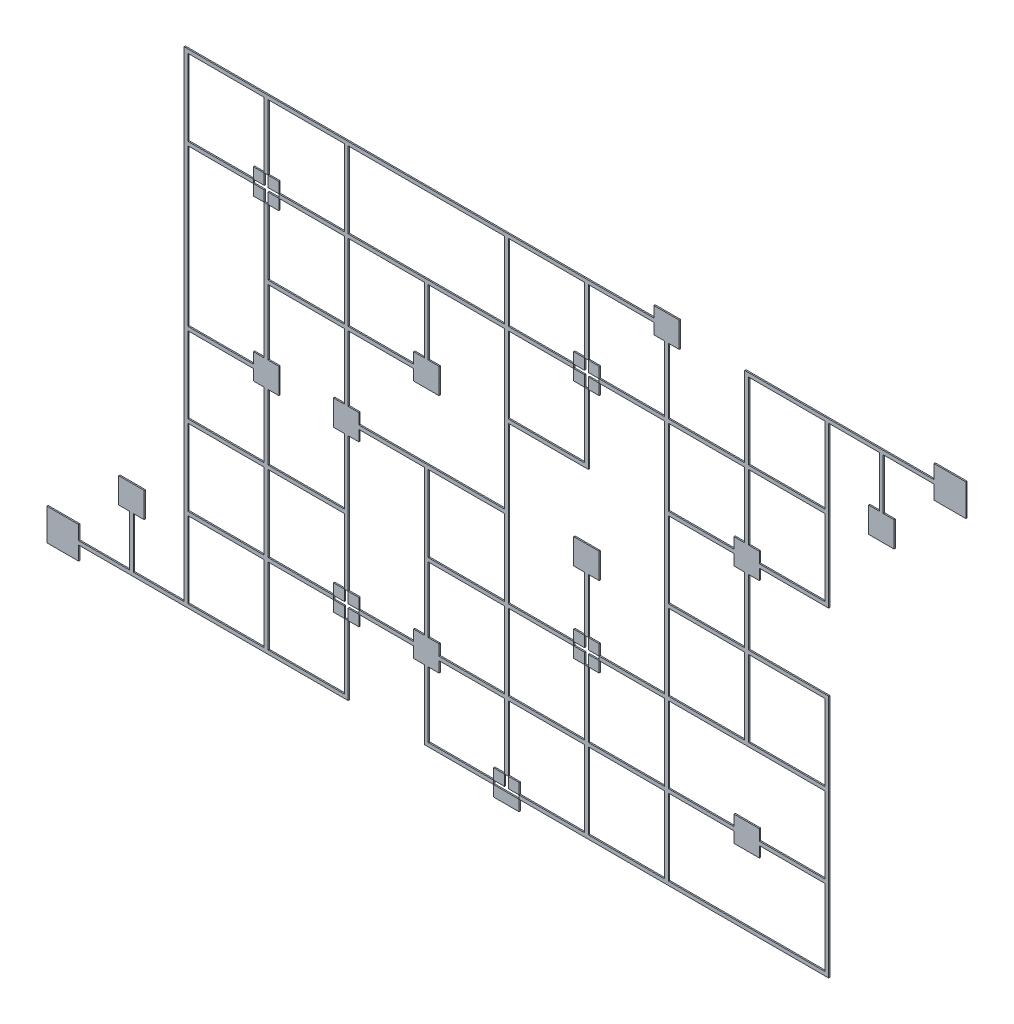
SolidWorks part; units mm, degrees
ref_plane "Front Plane" through (0, 0, 0) normal (0, 0, 1) x (1, 0, 0)
ref_plane "Top Plane" through (0, 0, 0) normal (0, 1, 0) x (1, 0, 0)
ref_plane "Right Plane" through (0, 0, 0) normal (1, 0, 0) x (0, 0, -1)
sketch "Sketch2" plane through (0, 0, 0) normal (0, 0, 1) x (1, 0, 0)
  line L1 (-2400, 2010) -> (2670, 2010)
  line L2 (-2400, 2010) -> (-2400, -1800)
  line L3 (-2400, -1800) -> (2670, -1800)
  line L4 (2670, 2010) -> (2670, -1800)
  dimension "D1" = 3810
  dimension "D2" = 5070
extrude "Boss-Extrude1" add sketch "Sketch2" along normal blind 10 contours L2 L3 L4 L1
sketch "Sketch3" plane through (0, 0, 10) normal (0, 0, 1) x (1, 0, 0)
  line L0 (-2400, 2010) -> (-2400, -1800) construction
  line L1 (-2370, 1980) -> (2640, 1980)
  line L2 (-2370, 1980) -> (-2370, -1770)
  line L3 (-2370, -1770) -> (2640, -1770)
  line L4 (2640, 1980) -> (2640, -1770)
  line L13 (-2400, -1800) -> (2670, -1800) construction
  line L14 (2670, 2010) -> (2670, -1800) construction
  line L15 (-2400, 2010) -> (2670, 2010) construction
  line L17 (-2370, 1980) -> (-1770, 1980)
  line L18 (-2370, 1980) -> (-2370, 1380)
  line L19 (-2370, 1380) -> (-1770, 1380)
  line L20 (-1770, 1980) -> (-1770, 1380)
  dimension "D1" = 30
  dimension "D2" = 30
  dimension "D3" = 30
  dimension "D4" = 30
  dimension "D5" = 600
  dimension "D6" = 600
sketch "Sketch4" plane through (0, 0, 0) normal (0, 0, 1) x (1, 0, 0)
extrude "Cut-Extrude14" cut sketch "Sketch3" against normal blind 20 contours L20 L1 L2 L19 region at (-2070, 1680, 10)
pattern_linear "LPattern2" count 8 spacing 630 along (1, 0, 0) count 6 spacing 630 along (0, -1, 0) of "Cut-Extrude14"
sketch "Sketch5" plane through (0, 0, 10) normal (0, 0, 1) x (1, 0, 0)
  line L0 (-2370, 1980) -> (-2370, 1380) construction
  line L1 (-1855, 1465) -> (-1655, 1465)
  line L2 (-1855, 1465) -> (-1855, 1265)
  line L3 (-1855, 1265) -> (-1655, 1265)
  line L4 (-1655, 1465) -> (-1655, 1265)
  line L6 (-2370, 1980) -> (-1770, 1980) construction
  dimension "D1" = 515
  dimension "D2" = 200
  dimension "D3" = 200
  dimension "D4" = 515
extrude "Boss-Extrude2" add sketch "Sketch5" against normal through all
sketch "Sketch6" plane through (0, 0, 0) normal (0, 0, 1) x (1, 0, 0)
  line L0 (-2370, -510) -> (-1770, -510) construction
  line L1 (-1855, 205) -> (-1655, 205)
  line L2 (-1855, 205) -> (-1855, 5)
  line L3 (-1855, 5) -> (-1655, 5)
  line L4 (-1655, 205) -> (-1655, 5)
  line L5 (-2370, 720) -> (-2370, 120) construction
  dimension "D1" = 515
  dimension "D2" = 200
  dimension "D3" = 200
  dimension "D4" = 515
extrude "Boss-Extrude3" add sketch "Sketch6" along normal blind 10
sketch "Sketch7" plane through (0, 0, 0) normal (0, 0, 1) x (1, 0, 0)
  line L0 (-1740, -510) -> (-1140, -510) construction
  line L1 (-1225, 205) -> (-1025, 205)
  line L2 (-1225, 205) -> (-1225, 5)
  line L3 (-1225, 5) -> (-1025, 5)
  line L4 (-1025, 205) -> (-1025, 5)
  line L5 (-510, 720) -> (-510, 120) construction
  dimension "D1" = 515
  dimension "D2" = 200
  dimension "D3" = 200
  dimension "D4" = 515
extrude "Boss-Extrude4" add sketch "Sketch7" along normal blind 10
sketch "Sketch8" plane through (0, 0, 0) normal (0, 0, 1) x (1, 0, 0)
  line L0 (-1740, -1770) -> (-1140, -1770) construction
  line L1 (-1225, -1055) -> (-1025, -1055)
  line L2 (-1225, -1055) -> (-1225, -1255)
  line L3 (-1225, -1255) -> (-1025, -1255)
  line L4 (-1025, -1055) -> (-1025, -1255)
  line L5 (-1740, -540) -> (-1740, -1140) construction
  dimension "D1" = 515
  dimension "D2" = 200
  dimension "D3" = 200
  dimension "D4" = 515
extrude "Boss-Extrude5" add sketch "Sketch8" along normal blind 10
sketch "Sketch9" plane through (0, 0, 0) normal (0, 0, 1) x (1, 0, 0)
  line L0 (-1110, -1770) -> (-510, -1770) construction
  line L1 (-595, -1055) -> (-395, -1055)
  line L2 (-595, -1055) -> (-595, -1255)
  line L3 (-595, -1255) -> (-395, -1255)
  line L4 (-395, -1055) -> (-395, -1255)
  line L5 (120, -540) -> (120, -1140) construction
  dimension "D1" = 515
  dimension "D2" = 200
  dimension "D3" = 200
  dimension "D4" = 515
extrude "Boss-Extrude6" add sketch "Sketch9" along normal blind 10
sketch "Sketch10" plane through (0, 0, 0) normal (0, 0, 1) x (1, 0, 0)
  line L0 (-1025, 120) -> (-510, 120) construction
  line L1 (-595, 835) -> (-395, 835)
  line L2 (-595, 835) -> (-595, 635)
  line L3 (-595, 635) -> (-395, 635)
  line L4 (-395, 835) -> (-395, 635)
  line L5 (-1110, 1350) -> (-1110, 750) construction
  dimension "D1" = 515
  dimension "D2" = 200
  dimension "D3" = 200
  dimension "D4" = 515
extrude "Boss-Extrude7" add sketch "Sketch10" along normal blind 10
sketch "Sketch11" plane through (0, 0, 0) normal (0, 0, 1) x (1, 0, 0)
  line L0 (150, 1980) -> (150, 1380) construction
  line L1 (665, 1465) -> (865, 1465)
  line L2 (665, 1465) -> (665, 1265)
  line L3 (665, 1265) -> (865, 1265)
  line L4 (865, 1465) -> (865, 1265)
  line L5 (150, 750) -> (750, 750) construction
  point P4 (665, 1365)
  dimension "D1" = 515
  dimension "D2" = 200
  dimension "D3" = 200
  dimension "D4" = 515
extrude "Boss-Extrude8" add sketch "Sketch11" along normal blind 10
sketch "Sketch12" plane through (0, 0, 0) normal (0, 0, 1) x (1, 0, 0)
  line L0 (865, 1380) -> (1380, 1380) construction
  line L1 (1295, 2095) -> (1495, 2095)
  line L2 (1295, 2095) -> (1295, 1895)
  line L3 (1295, 1895) -> (1495, 1895)
  line L4 (1495, 2095) -> (1495, 1895)
  line L5 (780, 1980) -> (780, 1465) construction
  dimension "D1" = 515
  dimension "D2" = 200
  dimension "D3" = 200
  dimension "D4" = 515
extrude "Boss-Extrude9" add sketch "Sketch12" along normal blind 10
sketch "Sketch13" plane through (0, 0, 0) normal (0, 0, 1) x (1, 0, 0)
  line L0 (1410, 120) -> (2010, 120) construction
  line L1 (1925, 835) -> (2125, 835)
  line L2 (1925, 835) -> (1925, 635)
  line L3 (1925, 635) -> (2125, 635)
  line L4 (2125, 835) -> (2125, 635)
  line L5 (1410, 1350) -> (1410, 750) construction
  dimension "D1" = 515
  dimension "D2" = 200
  dimension "D3" = 200
  dimension "D4" = 515
extrude "Boss-Extrude10" add sketch "Sketch13" along normal blind 10
sketch "Sketch14" plane through (0, 0, 0) normal (0, 0, 1) x (1, 0, 0)
  line L0 (150, 720) -> (150, 120) construction
  line L1 (665, 205) -> (865, 205)
  line L2 (665, 205) -> (665, 5)
  line L3 (665, 5) -> (865, 5)
  line L4 (865, 205) -> (865, 5)
  line L5 (150, -510) -> (750, -510) construction
  dimension "D1" = 515
  dimension "D2" = 200
  dimension "D3" = 200
  dimension "D4" = 515
extrude "Boss-Extrude11" add sketch "Sketch14" along normal blind 10
sketch "Sketch15" plane through (0, 0, 0) normal (0, 0, 1) x (1, 0, 0)
  line L0 (150, 90) -> (150, -510) construction
  line L1 (665, -425) -> (865, -425)
  line L2 (665, -425) -> (665, -625)
  line L3 (665, -625) -> (865, -625)
  line L4 (865, -425) -> (865, -625)
  line L5 (150, -1140) -> (750, -1140) construction
  dimension "D1" = 515
  dimension "D2" = 200
  dimension "D3" = 200
  dimension "D4" = 515
extrude "Boss-Extrude12" add sketch "Sketch15" along normal blind 10
sketch "Sketch17" plane through (0, 0, 0) normal (0, 0, 1) x (1, 0, 0)
  line L0 (1410, -540) -> (1410, -1140) construction
  line L1 (1925, -1055) -> (2125, -1055)
  line L2 (1925, -1055) -> (1925, -1255)
  line L3 (1925, -1255) -> (2125, -1255)
  line L4 (2125, -1055) -> (2125, -1255)
  line L5 (1410, -1770) -> (2010, -1770) construction
  dimension "D1" = 515
  dimension "D2" = 200
  dimension "D3" = 200
  dimension "D4" = 515
extrude "Boss-Extrude14" add sketch "Sketch17" along normal blind 10
sketch "Sketch18" plane through (0, 0, 0) normal (0, 0, 1) x (1, 0, 0)
  line L0 (-480, -1255) -> (-480, -1770) construction
  line L1 (35, -1685) -> (235, -1685)
  line L2 (35, -1685) -> (35, -1885)
  line L3 (35, -1885) -> (235, -1885)
  line L4 (235, -1685) -> (235, -1885)
  line L5 (-395, -1170) -> (120, -1170) construction
  dimension "D1" = 515
  dimension "D2" = 200
  dimension "D3" = 200
  dimension "D4" = 515
extrude "Boss-Extrude15" add sketch "Sketch18" along normal blind 10
sketch "Sketch19" plane through (0, 0, 0) normal (0, 0, 1) x (1, 0, 0)
  line L1 (-2915, -1170) -> (-2715, -1170)
  line L2 (-2915, -1170) -> (-2915, -1370)
  line L3 (-2915, -1370) -> (-2715, -1370)
  line L4 (-2715, -1170) -> (-2715, -1370)
  line L7 (-2400, -1800) -> (35, -1800) construction
  line L8 (-2400, 2010) -> (-2400, -1800) construction
  dimension "D1" = 430
  dimension "D2" = 200
  dimension "D3" = 200
  dimension "D4" = 315
sketch "Sketch20" plane through (0, 0, 0) normal (0, 0, 1) x (1, 0, 0)
  line L1 (2985, 1580) -> (3185, 1580)
  line L2 (2985, 1580) -> (2985, 1380)
  line L3 (2985, 1380) -> (3185, 1380)
  line L4 (3185, 1580) -> (3185, 1380)
  line L7 (2670, 2010) -> (2670, -1800) construction
  line L8 (1495, 2010) -> (2670, 2010) construction
  point P6 (3085, 1580)
  dimension "D1" = 315
  dimension "D2" = 200
  dimension "D3" = 200
  dimension "D4" = 430
sketch "Sketch21" plane through (0, 0, 0) normal (0, 0, 1) x (1, 0, 0)
  line L0 (-2400, 2010) -> (-2400, -1800) construction
  line L1 (-2400, -1800) -> (-3230, -1800)
  line L2 (-2400, -1800) -> (-2400, -1770)
  line L3 (-2400, -1770) -> (-3230, -1770)
  line L4 (-3230, -1800) -> (-3230, -1770)
  line L5 (-2400, -1800) -> (35, -1800) construction
  dimension "D1" = 830
  dimension "D2" = 30
  dimension "D3" = 0
extrude "Boss-Extrude18" add sketch "Sketch21" along normal blind 10 contours L3 L4 L1 L2
sketch "Sketch23" plane through (0, 0, 0) normal (0, 0, 1) x (1, 0, 0)
  line L0 (1495, 2010) -> (2670, 2010) construction
  line L1 (2670, 2010) -> (3500, 2010)
  line L2 (2670, 2010) -> (2670, 1980)
  line L3 (2670, 1980) -> (3500, 1980)
  line L4 (3500, 2010) -> (3500, 1980)
  dimension "D1" = 830
  dimension "D2" = 30
  dimension "D3" = 180
extrude "Boss-Extrude20" add sketch "Sketch23" along normal blind 10
sketch "Sketch24" plane through (0, 0, 0) normal (0, 0, 1) x (1, 0, 0)
  line L0 (-2400, -1770) -> (-3230, -1770) construction
  line L1 (-2800, -1770) -> (-2830, -1770)
  line L2 (-2800, -1770) -> (-2800, -1370)
  line L3 (-2800, -1370) -> (-2830, -1370)
  line L4 (-2830, -1770) -> (-2830, -1370)
  line L5 (-2400, 2010) -> (-2400, -1770) construction
  dimension "D1" = 400
  dimension "D2" = 30
  dimension "D3" = 400
extrude "Boss-Extrude21" add sketch "Sketch24" along normal blind 10
sketch "Sketch26" plane through (0, 0, 0) normal (0, 0, 1) x (1, 0, 0)
  line L0 (2670, 1980) -> (2670, -1800) construction
  line L1 (3070, 1980) -> (3100, 1980)
  line L2 (3070, 1980) -> (3070, 1580)
  line L3 (3070, 1580) -> (3100, 1580)
  line L4 (3100, 1980) -> (3100, 1580)
  line L5 (2670, 1980) -> (3500, 1980) construction
  dimension "D1" = 400
  dimension "D2" = 30
  dimension "D3" = 400
  dimension "D4" = 0
extrude "Boss-Extrude22" add sketch "Sketch26" along normal blind 10 contours L2 L3 L4 L1
sketch "Sketch27" plane through (0, 0, 0) normal (0, 0, 1) x (1, 0, 0)
  line L0 (-2400, 2010) -> (-2400, -1770) construction
  line L1 (-3480, -1660) -> (-3230, -1660)
  line L2 (-3480, -1660) -> (-3480, -1910)
  line L3 (-3480, -1910) -> (-3230, -1910)
  line L4 (-3230, -1660) -> (-3230, -1910)
  line L5 (-3230, -1800) -> (35, -1800) construction
  dimension "D1" = 250
  dimension "D2" = 250
  dimension "D3" = 830
  dimension "D4" = 110
extrude "Boss-Extrude23" add sketch "Sketch27" along normal blind 10
extrude "Boss-Extrude24" add sketch "Sketch19" along normal blind 10
extrude "Boss-Extrude25" add sketch "Sketch20" along normal blind 10
sketch "Sketch28" plane through (0, 0, 0) normal (0, 0, 1) x (1, 0, 0)
  line L0 (1495, 2010) -> (3500, 2010) construction
  line L1 (3500, 2120) -> (3750, 2120)
  line L2 (3500, 2120) -> (3500, 1870)
  line L3 (3500, 1870) -> (3750, 1870)
  line L4 (3750, 2120) -> (3750, 1870)
  line L5 (3500, 1980) -> (3500, 2010) construction
  dimension "D1" = 250
  dimension "D2" = 250
  dimension "D3" = 110
  dimension "D4" = 0
extrude "Boss-Extrude26" add sketch "Sketch28" along normal blind 10
sketch "Sketch39" plane through (0, 0, 0) normal (0, 0, 1) x (1, 0, 0)
  line L0 (-1655, 1465) -> (-1740, 1465) construction
  line L1 (-1770, 1464.999) -> (-1740, 1464.999)
  line L2 (-1770, 1464.999) -> (-1770, 1265.001)
  line L3 (-1770, 1265.001) -> (-1740, 1265.001)
  line L4 (-1740, 1464.999) -> (-1740, 1265.001)
  line L5 (-1740, 1265) -> (-1655, 1265) construction
  line L6 (-1770, 1980) -> (-1770, 1465) construction
  dimension "D1" = 0.001
  dimension "D2" = 0.001
  dimension "D3" = 30
  dimension "D4" = 0
extrude "Cut-Extrude108" cut sketch "Sketch39" along normal blind 10
sketch "Sketch40" plane through (0, 0, 0) normal (0, 0, 1) x (1, 0, 0)
  line L0 (-1855, 1465) -> (-1855, 1380) construction
  line L1 (-1854.999, 1380) -> (-1655.001, 1380)
  line L2 (-1854.999, 1380) -> (-1854.999, 1350)
  line L3 (-1854.999, 1350) -> (-1655.001, 1350)
  line L4 (-1655.001, 1380) -> (-1655.001, 1350)
  line L5 (-1655, 1380) -> (-1655, 1465) construction
  line L6 (-2370, 1350) -> (-1855, 1350) construction
  dimension "D1" = 0.001
  dimension "D2" = 0.001
  dimension "D3" = 30
  dimension "D4" = 0
extrude "Cut-Extrude109" cut sketch "Sketch40" along normal blind 10
sketch "Sketch41" plane through (0, 0, 0) normal (0, 0, 1) x (1, 0, 0)
  line L0 (865, 1465) -> (780, 1465) construction
  line L5 (750, 1464.999) -> (780, 1464.999)
  line L6 (750, 1464.999) -> (750, 1265.001)
  line L7 (750, 1265.001) -> (780, 1265.001)
  line L8 (780, 1464.999) -> (780, 1265.001)
  line L9 (780, 1265) -> (865, 1265) construction
  line L10 (750, 1980) -> (750, 1465) construction
  dimension "D1" = 0.001
  dimension "D2" = 0.001
  dimension "D3" = 30
  dimension "D4" = 0
extrude "Cut-Extrude110" cut sketch "Sketch41" along normal blind 10
sketch "Sketch42" plane through (0, 0, 0) normal (0, 0, 1) x (1, 0, 0)
  line L0 (665, 1465) -> (665, 1380) construction
  line L1 (665.001, 1380) -> (864.999, 1380)
  line L2 (665.001, 1380) -> (665.001, 1350)
  line L3 (665.001, 1350) -> (864.999, 1350)
  line L4 (864.999, 1380) -> (864.999, 1350)
  line L5 (865, 1380) -> (865, 1465) construction
  line L6 (150, 1350) -> (665, 1350) construction
  dimension "D1" = 0.001
  dimension "D2" = 0.001
  dimension "D3" = 30
  dimension "D4" = 0
extrude "Cut-Extrude111" cut sketch "Sketch42" along normal blind 10
sketch "Sketch43" plane through (0, 0, 0) normal (0, 0, 1) x (1, 0, 0)
  line L0 (-1025, -1055) -> (-1110, -1055) construction
  line L1 (-1140, -1055.001) -> (-1110, -1055.001)
  line L2 (-1140, -1055.001) -> (-1140, -1254.999)
  line L3 (-1140, -1254.999) -> (-1110, -1254.999)
  line L4 (-1110, -1055.001) -> (-1110, -1254.999)
  line L5 (-1110, -1255) -> (-1025, -1255) construction
  line L6 (-1140, -540) -> (-1140, -1055) construction
  dimension "D1" = 0.001
  dimension "D2" = 0.001
  dimension "D3" = 30
  dimension "D4" = 0
extrude "Cut-Extrude112" cut sketch "Sketch43" along normal blind 10
sketch "Sketch44" plane through (0, 0, 0) normal (0, 0, 1) x (1, 0, 0)
  line L0 (-1025, -1140) -> (-1025, -1055) construction
  line L1 (-1224.999, -1140) -> (-1025.001, -1140)
  line L2 (-1224.999, -1140) -> (-1224.999, -1170)
  line L3 (-1224.999, -1170) -> (-1025.001, -1170)
  line L4 (-1025.001, -1140) -> (-1025.001, -1170)
  line L5 (-1225, -1055) -> (-1225, -1140) construction
  line L6 (-1740, -1170) -> (-1225, -1170) construction
  point P4 (-1025.001, -1155)
  dimension "D1" = 0.001
  dimension "D2" = 0.001
  dimension "D3" = 30
  dimension "D4" = 0
extrude "Cut-Extrude113" cut sketch "Sketch44" along normal blind 10
sketch "Sketch45" plane through (0, 0, 0) normal (0, 0, 1) x (1, 0, 0)
  line L0 (865, -510) -> (865, -425) construction
  line L1 (665.001, -510) -> (864.999, -510)
  line L2 (665.001, -510) -> (665.001, -540)
  line L3 (665.001, -540) -> (864.999, -540)
  line L4 (864.999, -510) -> (864.999, -540)
  line L5 (665, -425) -> (665, -510) construction
  line L6 (150, -540) -> (665, -540) construction
  dimension "D1" = 0.001
  dimension "D2" = 0.001
  dimension "D3" = 30
  dimension "D4" = 0
extrude "Cut-Extrude114" cut sketch "Sketch45" along normal blind 10
sketch "Sketch46" plane through (0, 0, 0) normal (0, 0, 1) x (1, 0, 0)
  line L0 (865, -425) -> (780, -425) construction
  line L1 (750, -425.001) -> (780, -425.001)
  line L2 (750, -425.001) -> (750, -624.999)
  line L3 (750, -624.999) -> (780, -624.999)
  line L4 (780, -425.001) -> (780, -624.999)
  line L9 (780, -625) -> (865, -625) construction
  line L10 (750, 5) -> (750, -425) construction
  point P6 (822.5, -425)
  dimension "D1" = 0.001
  dimension "D2" = 0.001
  dimension "D3" = 30
  dimension "D4" = 0
extrude "Cut-Extrude115" cut sketch "Sketch46" along normal blind 10
sketch "Sketch47" plane through (0, 0, 0) normal (0, 0, 1) x (1, 0, 0)
  line L0 (235, -1770) -> (235, -1685) construction
  line L1 (35.001, -1770) -> (234.999, -1770)
  line L2 (35.001, -1770) -> (35.001, -1800)
  line L3 (35.001, -1800) -> (234.999, -1800)
  line L4 (234.999, -1770) -> (234.999, -1800)
  line L5 (35, -1685) -> (35, -1770) construction
  line L6 (-480, -1770) -> (35, -1770) construction
  point P4 (234.999, -1785)
  dimension "D1" = 0.001
  dimension "D2" = 0.001
  dimension "D3" = 30
  dimension "D4" = 0
extrude "Cut-Extrude116" cut sketch "Sketch47" along normal blind 10
sketch "Sketch48" plane through (0, 0, 0) normal (0, 0, 1) x (1, 0, 0)
  line L0 (234.999, -1770) -> (35.001, -1770) construction
  line L1 (120, -1685.001) -> (150, -1685.001)
  line L2 (120, -1685.001) -> (120, -1770)
  line L3 (120, -1770) -> (150, -1770)
  line L4 (150, -1685.001) -> (150, -1770)
  line L5 (235, -1685) -> (150, -1685) construction
  line L6 (120, -1170) -> (120, -1685) construction
  line L7 (35.001, -1800) -> (234.999, -1800) construction
  dimension "D1" = 0.001
  dimension "D2" = 30
  dimension "D3" = 0
  dimension "D4" = 30
extrude "Cut-Extrude117" cut sketch "Sketch48" along normal blind 10
sketch "Sketch49" plane through (0, 0, 0) normal (0, 0, 1) x (1, 0, 0)
  line L0 (-480, 1980) -> (120, 1980) construction
  line L1 (-510, 1979.999) -> (-480, 1979.999)
  line L2 (-510, 1979.999) -> (-510, 1380.001)
  line L3 (-510, 1380.001) -> (-480, 1380.001)
  line L4 (-480, 1979.999) -> (-480, 1380.001)
  line L5 (-480, 1380) -> (120, 1380) construction
  line L6 (-510, 1980) -> (-510, 1380) construction
  dimension "D1" = 0.001
  dimension "D2" = 0.001
  dimension "D3" = 30
  dimension "D4" = 0
extrude "Cut-Extrude118" cut sketch "Sketch49" along normal blind 10
sketch "Sketch50" plane through (0, 0, 0) normal (0, 0, 1) x (1, 0, 0)
  line L0 (1495, 2010) -> (1495, 2095) construction
  line L1 (1495.001, 2010) -> (2009.999, 2010)
  line L2 (1495.001, 2010) -> (1495.001, 1980)
  line L3 (1495.001, 1980) -> (2009.999, 1980)
  line L4 (2009.999, 2010) -> (2009.999, 1980)
  line L5 (2010, 1980) -> (2010, 1380) construction
  line L6 (1495, 1980) -> (2010, 1980) construction
  dimension "D1" = 0.001
  dimension "D2" = 0.001
  dimension "D3" = 30
  dimension "D4" = 0
extrude "Cut-Extrude119" cut sketch "Sketch50" along normal blind 10
sketch "Sketch52" plane through (0, 0, 0) normal (0, 0, 1) x (1, 0, 0)
  line L0 (-2370, 1350) -> (-2370, 750) construction
  line L1 (-2369.999, 750) -> (-1770.001, 750)
  line L2 (-2369.999, 750) -> (-2369.999, 720)
  line L3 (-2369.999, 720) -> (-1770.001, 720)
  line L4 (-1770.001, 750) -> (-1770.001, 720)
  line L5 (-1770, 1265) -> (-1770, 750) construction
  line L6 (-2370, 720) -> (-1770, 720) construction
  dimension "D1" = 0.001
  dimension "D2" = 0.001
  dimension "D3" = 30
  dimension "D4" = 0
extrude "Cut-Extrude120" cut sketch "Sketch52" along normal blind 10
sketch "Sketch53" plane through (0, 0, 0) normal (0, 0, 1) x (1, 0, 0)
  line L0 (-1655, 120) -> (-1655, 205) construction
  line L1 (-1654.999, 120) -> (-1225.001, 120)
  line L2 (-1654.999, 120) -> (-1654.999, 90)
  line L3 (-1654.999, 90) -> (-1225.001, 90)
  line L4 (-1225.001, 120) -> (-1225.001, 90)
  line L5 (-1225, 205) -> (-1225, 120) construction
  line L6 (-1655, 90) -> (-1225, 90) construction
  dimension "D1" = 0.001
  dimension "D2" = 0.001
  dimension "D3" = 30
  dimension "D4" = 0
extrude "Cut-Extrude121" cut sketch "Sketch53" along normal blind 10
sketch "Sketch54" plane through (0, 0, 0) normal (0, 0, 1) x (1, 0, 0)
  line L0 (-1110, -540) -> (-510, -540) construction
  line L1 (-1109.999, -510) -> (-510.001, -510)
  line L2 (-1109.999, -510) -> (-1109.999, -540)
  line L3 (-1109.999, -540) -> (-510.001, -540)
  line L4 (-510.001, -510) -> (-510.001, -540)
  line L5 (-1110, 5) -> (-1110, -510) construction
  line L6 (-510, 90) -> (-510, -510) construction
  dimension "D1" = 0.001
  dimension "D2" = 0.001
  dimension "D3" = 30
extrude "Cut-Extrude122" cut sketch "Sketch54" along normal blind 10
sketch "Sketch55" plane through (0, 0, 0) normal (0, 0, 1) x (1, 0, 0)
  line L0 (-1110, -1255) -> (-1110, -1770) construction
  line L1 (-1109.999, -1770) -> (-510.001, -1770)
  line L2 (-1109.999, -1770) -> (-1109.999, -1800)
  line L3 (-1109.999, -1800) -> (-510.001, -1800)
  line L4 (-510.001, -1770) -> (-510.001, -1800)
  line L5 (-510, -1255) -> (-510, -1770) construction
  line L6 (-1110, -1770) -> (-510, -1770) construction
  dimension "D1" = 0.001
  dimension "D2" = 0.001
  dimension "D3" = 30
  dimension "D4" = 0
extrude "Cut-Extrude123" cut sketch "Sketch55" along normal blind 10
sketch "Sketch56" plane through (0, 0, 0) normal (0, 0, 1) x (1, 0, 0)
  line L0 (-510, 635) -> (-510, 120) construction
  line L1 (-510, 634.999) -> (-480, 634.999)
  line L2 (-510, 634.999) -> (-510, 120.001)
  line L3 (-510, 120.001) -> (-480, 120.001)
  line L4 (-480, 634.999) -> (-480, 120.001)
  line L5 (-480, 635) -> (-395, 635) construction
  line L6 (-480, 120) -> (120, 120) construction
  point P8 (-495, 120.001)
  dimension "D1" = 0.001
  dimension "D2" = 0.001
  dimension "D3" = 30
extrude "Cut-Extrude124" cut sketch "Sketch56" along normal blind 10
sketch "Sketch57" plane through (0, 0, 0) normal (0, 0, 1) x (1, 0, 0)
  line L0 (-395, 720) -> (120, 720) construction
  line L1 (-394.999, 750) -> (119.999, 750)
  line L2 (-394.999, 750) -> (-394.999, 720)
  line L3 (-394.999, 720) -> (119.999, 720)
  line L4 (119.999, 750) -> (119.999, 720)
  line L5 (-395, 750) -> (-395, 835) construction
  line L6 (120, 1350) -> (120, 750) construction
  dimension "D1" = 0.001
  dimension "D2" = 0.001
  dimension "D3" = 30
extrude "Cut-Extrude125" cut sketch "Sketch57" along normal blind 10
sketch "Sketch58" plane through (0, 0, 0) normal (0, 0, 1) x (1, 0, 0)
  line L0 (150, 720) -> (150, 120) construction
  line L1 (150.001, 120) -> (664.999, 120)
  line L2 (150.001, 120) -> (150.001, 90)
  line L3 (150.001, 90) -> (664.999, 90)
  line L4 (664.999, 120) -> (664.999, 90)
  line L5 (665, 205) -> (665, 120) construction
  line L6 (150, 120) -> (665, 120) construction
  dimension "D1" = 0.001
  dimension "D2" = 0.001
  dimension "D3" = 30
  dimension "D4" = 0
extrude "Cut-Extrude126" cut sketch "Sketch58" along normal blind 10
sketch "Sketch59" plane through (0, 0, 0) normal (0, 0, 1) x (1, 0, 0)
  line L0 (865, 120) -> (1380, 120) construction
  line L1 (865.001, 120) -> (1379.999, 120)
  line L2 (865.001, 120) -> (865.001, 90)
  line L3 (865.001, 90) -> (1379.999, 90)
  line L4 (1379.999, 120) -> (1379.999, 90)
  line L5 (865, 120) -> (865, 205) construction
  line L6 (1380, 720) -> (1380, 120) construction
  dimension "D1" = 0.001
  dimension "D2" = 0.001
  dimension "D3" = 30
extrude "Cut-Extrude127" cut sketch "Sketch59" along normal blind 10
sketch "Sketch60" plane through (0, 0, 0) normal (0, 0, 1) x (1, 0, 0)
  line L0 (750, 720) -> (750, 205) construction
  line L1 (750, 719.999) -> (780, 719.999)
  line L2 (750, 719.999) -> (750, 205.001)
  line L3 (750, 205.001) -> (780, 205.001)
  line L4 (780, 719.999) -> (780, 205.001)
  line L5 (780, 720) -> (1380, 720) construction
  line L6 (865, 205) -> (780, 205) construction
  dimension "D1" = 0.001
  dimension "D2" = 0.001
  dimension "D3" = 30
extrude "Cut-Extrude128" cut sketch "Sketch60" along normal blind 10
sketch "Sketch61" plane through (0, 0, 0) normal (0, 0, 1) x (1, 0, 0)
  line L0 (780, 1265) -> (780, 750) construction
  line L1 (780.001, 750) -> (1379.999, 750)
  line L2 (780.001, 750) -> (780.001, 720)
  line L3 (780.001, 720) -> (1379.999, 720)
  line L4 (1379.999, 750) -> (1379.999, 720)
  line L5 (1380, 1350) -> (1380, 750) construction
  line L6 (780, 750) -> (1380, 750) construction
  dimension "D1" = 0.001
  dimension "D2" = 0.001
  dimension "D3" = 30
  dimension "D4" = 0
extrude "Cut-Extrude129" cut sketch "Sketch61" along normal blind 10
sketch "Sketch62" plane through (0, 0, 0) normal (0, 0, 1) x (1, 0, 0)
  line L0 (2125, 720) -> (2640, 720) construction
  line L1 (2640, 719.999) -> (2670, 719.999)
  line L2 (2640, 719.999) -> (2640, 120.001)
  line L3 (2640, 120.001) -> (2670, 120.001)
  line L4 (2670, 719.999) -> (2670, 120.001)
  line L5 (2040, 120) -> (2640, 120) construction
  line L6 (2670, 1980) -> (2670, -1800) construction
  dimension "D1" = 0.001
  dimension "D2" = 0.001
  dimension "D3" = 30
  dimension "D4" = 0
extrude "Cut-Extrude130" cut sketch "Sketch62" along normal blind 10
sketch "Sketch63" plane through (0, 0, 0) normal (0, 0, 1) x (1, 0, 0)
  line L0 (2040, -540) -> (2640, -540) construction
  line L1 (2010, -540.001) -> (2040, -540.001)
  line L2 (2010, -540.001) -> (2010, -1054.999)
  line L3 (2010, -1054.999) -> (2040, -1054.999)
  line L4 (2040, -540.001) -> (2040, -1054.999)
  line L5 (2125, -1055) -> (2040, -1055) construction
  line L6 (2040, -540) -> (2040, -1055) construction
  dimension "D1" = 0.001
  dimension "D2" = 0.001
  dimension "D3" = 30
  dimension "D4" = 0
extrude "Cut-Extrude131" cut sketch "Sketch63" along normal blind 10
sketch "Sketch64" plane through (0, 0, 0) normal (0, 0, 1) x (1, 0, 0)
  line L0 (2040, -1255) -> (2125, -1255) construction
  line L1 (2010, -1255.001) -> (2040, -1255.001)
  line L2 (2010, -1255.001) -> (2010, -1769.999)
  line L3 (2010, -1769.999) -> (2040, -1769.999)
  line L4 (2040, -1255.001) -> (2040, -1769.999)
  line L5 (2040, -1770) -> (2640, -1770) construction
  line L6 (2040, -1255) -> (2040, -1770) construction
  dimension "D1" = 0.001
  dimension "D2" = 0.001
  dimension "D3" = 30
  dimension "D4" = 0
extrude "Cut-Extrude132" cut sketch "Sketch64" along normal blind 10
